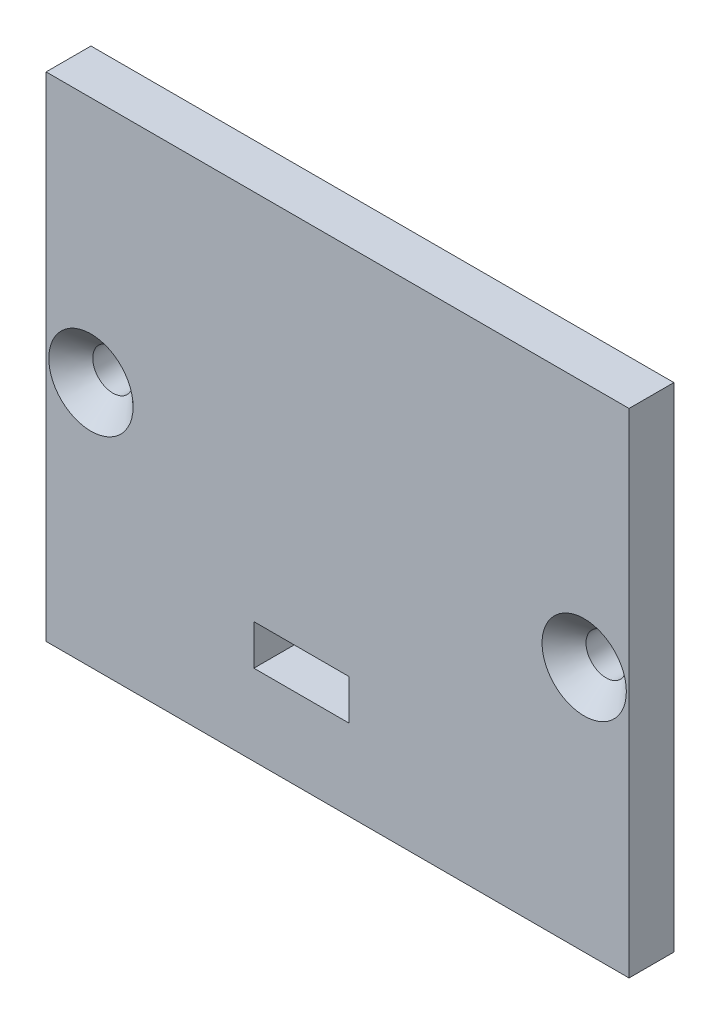
SolidWorks part; units mm, degrees
ref_plane "Plan de face" through (0, 0, 0) normal (0, 0, 1) x (1, 0, 0)
ref_plane "Plan de dessus" through (0, 0, 0) normal (0, 1, 0) x (1, 0, 0)
ref_plane "Plan de droite" through (0, 0, 0) normal (1, 0, 0) x (0, 0, -1)
sketch "Esquisse1" plane through (0, 0, 0) normal (0, 0, 1) x (1, 0, 0)
  line L1 (0, 0) -> (65, 0)
  line L2 (0, 0) -> (0, 55)
  line L3 (0, 55) -> (65, 55)
  line L4 (65, 0) -> (65, 55)
  dimension "D1" = 65
  dimension "D2" = 55
extrude "Boss.-Extru.1" add sketch "Esquisse1" along normal blind 5
sketch "Esquisse2" plane through (0, 0, 5) normal (0, 0, 1) x (1, 0, 0)
  line L0 (0, 55) -> (5, 55) construction
  line L1 (65, 55) -> (0, 55) construction
  line L2 (5, 55) -> (5, 0) construction
  line L3 (0, 0) -> (65, 0) construction
  line L4 (0, 55) -> (0, 0) construction
  line L5 (0, 0) -> (0, 27.5) construction
  line L6 (0, 27.5) -> (65, 27.5) construction
  line L7 (65, 0) -> (65, 55) construction
  line L8 (0, 55) -> (65, 55) construction
  line L9 (65, 55) -> (32.5, 55) construction
  line L10 (32.5, 55) -> (32.5, 0) construction
  circle A0 centre (5, 27.5) radius 2
  circle A1 centre (60, 27.5) radius 2
  dimension "D2" = 4
  dimension "D1" = 5
extrude "Enlèv. mat.-Extru.1" cut sketch "Esquisse2" against normal through all
hole_wizard "Fraisage pour vis à tête fraisée M41" positions "Esquisse5" profile "Esquisse4" countersink size "M4" standard "Ansi Metric" end condition through all
sketch "Esquisse5" plane through (0, 0, 5) normal (0, 0, 1) x (1, 0, 0)
  point P0 (5, 27.5)
  point P3 (60, 27.5)
sketch "Esquisse4" plane through (5, 27.5, 5) normal (1, 0, 0) x (0, -1, 0)
  line L0 (0, 0) -> (0, 5)
  line L1 (0, 5) -> (2.25, 5)
  line L2 (2.25, 5) -> (2.25, 2.45)
  line L3 (2.25, 2.45) -> (4.7, 0)
  line L5 (4.7, 0) -> (0, 0)
  line L6 (-2.25, 2.45) -> (-4.7, 0) construction
  line L11 (0, -6.35) -> (0, 107.95) construction
  dimension "Diamètre du perçage jusqu'au prochain" = 4.5
  dimension "Profondeur du perçage jusqu'au prochain" = 5
  dimension "Diamètre du fraisage entrant" = 9.4
  dimension "Angle du fraisage entrant" = 90
sketch "Esquisse6" plane through (0, 0, 5) normal (0, 0, 1) x (1, 0, 0)
  line L0 (0, 0) -> (0, 9) construction
  line L1 (0, 55) -> (0, 0) construction
  line L2 (0, 9) -> (65, 9) construction
  line L3 (65, 0) -> (65, 55) construction
  line L4 (65, 9) -> (65, 0) construction
  line L5 (0, 9) -> (32.5, 9) construction
  line L6 (0, 9) -> (23.1684, 9) construction
  line L7 (65, 9) -> (33.7684, 9) construction
  line L8 (23.1684, 9) -> (23.1684, 13.5)
  line L9 (23.1684, 13.5) -> (33.7684, 13.5)
  line L10 (33.7684, 13.5) -> (33.7684, 9)
  line L11 (33.7684, 9) -> (23.1684, 9)
  line L12 (0, 9) -> (33.7684, 9) construction
  line L13 (65, 9) -> (32.5, 9) construction
  dimension "D1" = 9
  dimension "D2" = 9
  dimension "D3" = 32.5
  dimension "D5" = 4.5
extrude "Enlèv. mat.-Extru.2" cut sketch "Esquisse6" against normal through all
